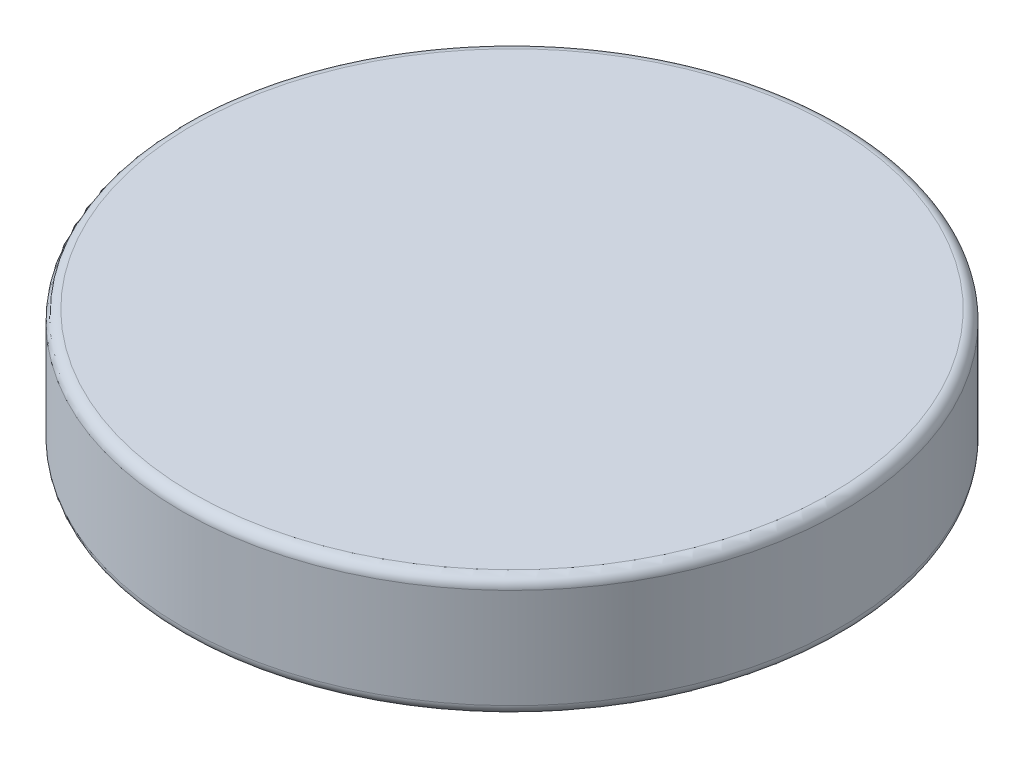
SolidWorks part; units mm, degrees
ref_plane "Front Plane" through (0, 0, 0) normal (0, 0, 1) x (1, 0, 0)
ref_plane "Top Plane" through (0, 0, 0) normal (0, 1, 0) x (1, 0, 0)
ref_plane "Right Plane" through (0, 0, 0) normal (1, 0, 0) x (0, 0, -1)
sketch "Sketch1" plane through (0, 0, 0) normal (0, 1, 0) x (1, 0, 0)
  circle A0 centre (0, 0) radius 15.9385
  dimension "D1" = 31.877
extrude "Boss-Extrude1" add sketch "Sketch1" along normal blind 5.842 contours A0
fillet "Fillet1" radius 0.508 2 edges at (0, 0, 15.9385) (0, 5.842, 15.9385)
